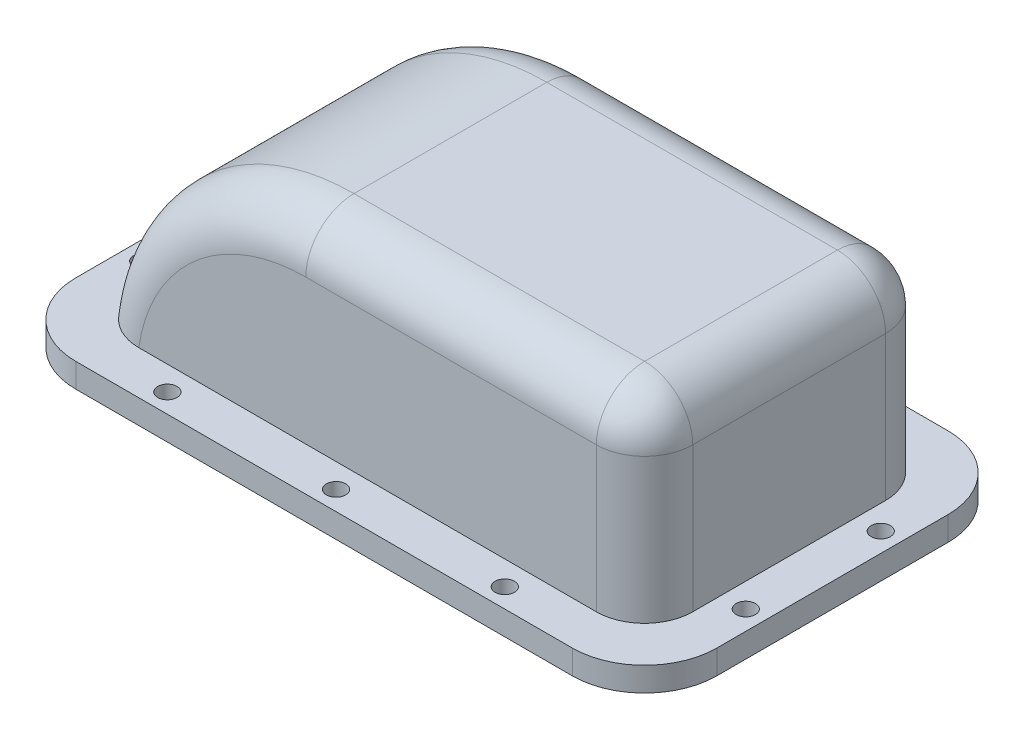
SolidWorks part; units mm, degrees
ref_plane "Front Plane" through (0, 0, 0) normal (0, 0, 1) x (1, 0, 0)
ref_plane "Top Plane" through (0, 0, 0) normal (0, 1, 0) x (1, 0, 0)
ref_plane "Right Plane" through (0, 0, 0) normal (1, 0, 0) x (0, 0, -1)
sketch "Sketch1" plane through (0, 0, 0) normal (0, 1, 0) x (1, 0, 0)
  line L1 (-133, -78) -> (133, -78)
  line L2 (-133, -78) -> (-133, 78)
  line L3 (-133, 78) -> (133, 78)
  line L4 (133, -78) -> (133, 78)
  line L5 (-133, -78) -> (133, 78) construction
  line L6 (-133, 78) -> (133, -78) construction
  point P0 (0, 0)
  dimension "D1" = 156
  dimension "D2" = 266
extrude "Boss-Extrude1" add sketch "Sketch1" along normal blind 10
sketch "Sketch2" plane through (0, 0, 0) normal (0, 0, 1) x (1, 0, 0)
  line L0 (-115, 10) -> (-115, 90)
  line L1 (-133, 10) -> (133, 10) construction
  line L2 (-115, 90) -> (115, 90)
  line L3 (115, 90) -> (115, 10)
  line L4 (-133, 10) -> (133, 10)
  line L5 (-133, 0) -> (133, 0) construction
  line L6 (133, 10) -> (133, 0) construction
  line L7 (-133, 10) -> (-133, 0) construction
  dimension "D1" = 90
  dimension "D2" = 18
  dimension "D3" = 18
extrude "Boss-Extrude2" add sketch "Sketch2" along normal mid plane 120 contours L0 L4 L3 L2 region at (0, 50, 0)
fillet "Fillet1" radius 90 1 edges at (-115, 90, 0)
fillet "Fillet2" radius 20 7 edges at (-85.5573, 67.082, -60) (-85.5573, 67.082, 60) (115, 50, -60) (115, 50, 60) (44.7214, 90, -60) (44.7214, 90, 60) (115, 90, 0)
sketch "Sketch3" plane through (0, 0, 0) normal (0, 0, 1) x (1, 0, 0)
  line L1 (115, 70) -> (115, 10) construction
  line L2 (-105.5573, 0) -> (105, 0)
  line L7 (-25.5573, 90) -> (95, 90) construction
  line L16 (-25.5573, 80) -> (85, 80)
  line L17 (105, 60) -> (105, 0)
  line L18 (-133, 0) -> (133, 0) construction
  arc A1 (-25.5573, 90) -> (-115, 10) centre (-25.5573, 0) ccw construction
  arc A4 (-25.5573, 80) -> (-105.5573, 0) centre (-25.5573, 0) ccw
  arc A5 (85, 80) -> (105, 60) centre (85, 60) cw
  dimension "D3" = 10
  dimension "D4" = 20
  dimension "D1" = 10
  dimension "D2" = 10
extrude "Cut-Extrude1" cut sketch "Sketch3" against normal offset from surface 20 and the other way offset from surface 20 up to face at (14.6047, 43.2288, -60) other way up to face at (14.6047, 43.2288, 60)
fillet "Fillet3" radius 10 8 edges at (105, 30, 40) (99.1421, 74.1421, 40) (-82.1258, 56.5685, 40) (-82.1258, 56.5685, -40) (105, 30, -40) (99.1421, 74.1421, -40) (29.7214, 80, 40) (29.7214, 80, -40)
sketch "Sketch4" plane through (0, 0, -78) normal (0, 0, -1) x (-1, 0, 0)
  line L1 (133, 0) -> (-133, 0) construction
  line L3 (133, 10) -> (133, 0) construction
  circle A0 centre (-5, -3) radius 20
  point P7 (0, 0)
  dimension "D1" = 40
  dimension "D2" = 3
  dimension "D3" = 138
extrude "Cut-Extrude2" cut sketch "Sketch4" against normal up to next
sketch "Sketch5" plane through (0, 0, -78) normal (0, 0, -1) x (-1, 0, 0)
  line L0 (95.5573, 0) -> (-95, 0) construction
  line L1 (-39.75, -19.0818) -> (29.75, -19.0818)
  line L2 (-39.75, -19.0818) -> (-39.75, 19.0818)
  line L3 (-39.75, 19.0818) -> (29.75, 19.0818)
  line L4 (29.75, -19.0818) -> (29.75, 19.0818)
  line L5 (-39.75, -19.0818) -> (29.75, 19.0818) construction
  line L6 (-39.75, 19.0818) -> (29.75, -19.0818) construction
  line L7 (133, 10) -> (133, 0) construction
  point P0 (-5, 0)
  point P5 (0, 0)
  point P6 (6.1387, 0)
  dimension "D1" = 69.5
  dimension "D2" = 138
extrude "Cut-Extrude3" cut sketch "Sketch5" against normal up to surface (18 mm away) up to face at (11.4031, 33.3192, -60)
sketch "Sketch6" plane through (0, 0, 0) normal (0, -1, 0) x (1, 0, 0)
  line L0 (0, 0) -> (-133, 0) construction
  line L1 (-133, -78) -> (-133, 78) construction
  line L2 (-133, 0) -> (-105.5573, 0) construction
  line L3 (-105.5573, -30) -> (-105.5573, 30) construction
  line L4 (-105.5573, 0) -> (-119.2786, 0) construction
  line L5 (0, 0) -> (0, -81.8254) construction
  line L6 (-119.2786, -46.2727) -> (-119.2786, 60.1138) construction
  line L7 (-29.75, -78) -> (-133, -78) construction
  circle A0 centre (-125, -28) radius 4
  circle A1 centre (125, -28) radius 4
  circle A2 centre (125, 28) radius 4
  circle A3 centre (-125, 28) radius 4
  circle A4 centre (-73, -70) radius 4
  circle A6 centre (67, -70) radius 4
  circle A7 centre (-3, 70) radius 4
  circle A8 centre (67, 70) radius 4
  circle A9 centre (-73, 70) radius 4
  circle A10 centre (-3, -70) radius 4 [skipped]
  point P24 (0, 0)
  point P25 (67, 70)
  point P26 (0, 0)
  point P27 (0, 0)
  dimension "D1" = 8
  dimension "D6" = 8
  dimension "D10" = 140
  dimension "D2" = 50
  dimension "D3" = 8
  dimension "D7" = 60
  dimension "D11" = 140
  dimension "D12" = 250
  dimension "D4" = 2
  dimension "D5" = 2
  dimension "D8" = 3
  dimension "D9" = 2
extrude "Cut-Extrude4" cut sketch "Sketch6" against normal through all
fillet "Fillet4" radius 30 4 edges at (-133, 5, 78) (133, 5, 78) (133, 5, -78) (-133, 5, -78)
